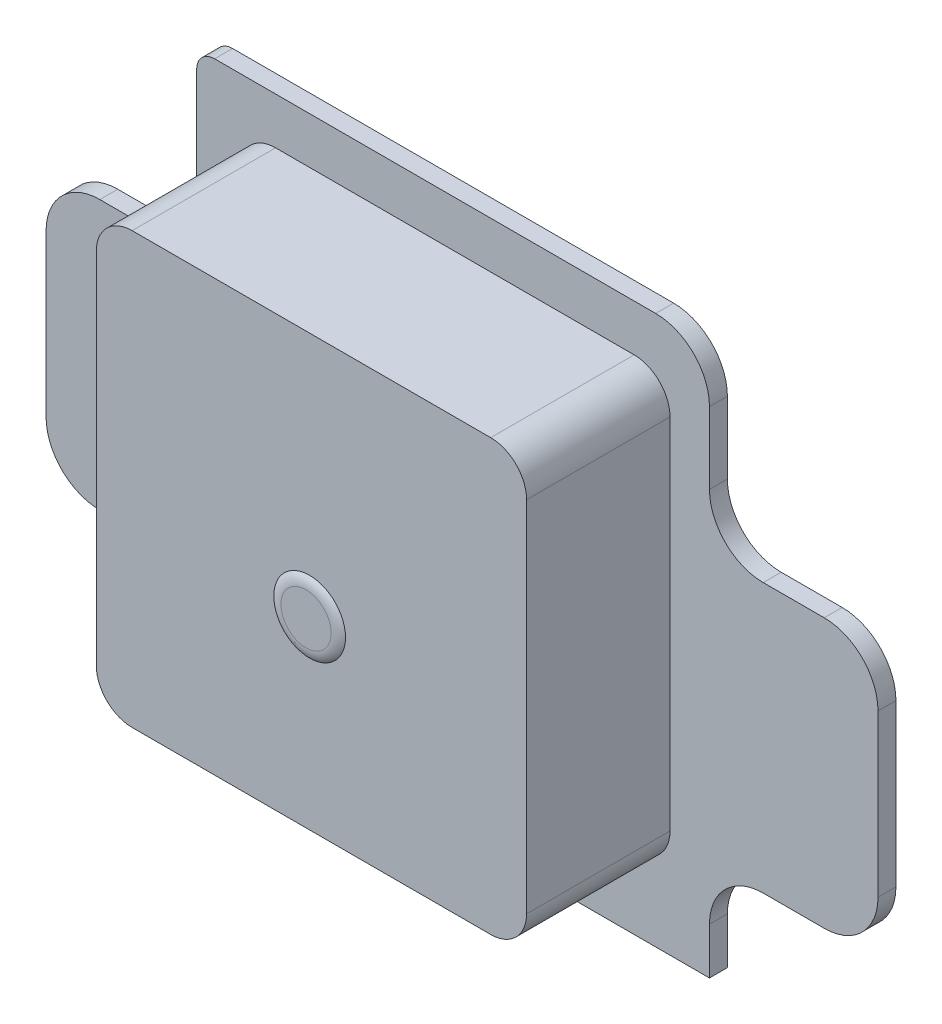
SolidWorks part; units mm, degrees
ref_plane "正面" through (0, 0, 0) normal (0, 0, 1) x (1, 0, 0)
ref_plane "平面" through (0, 0, 0) normal (0, 1, 0) x (1, 0, 0)
ref_plane "右側面" through (0, 0, 0) normal (1, 0, 0) x (0, 0, -1)
sketch "ｽｹｯﾁ1" plane through (0, 0, 0) normal (0, 0, 1) x (1, 0, 0)
  line L1 (-7.15, -7.65) -> (7.15, -7.65)
  line L2 (-7.15, -7.65) -> (-7.15, 7.65)
  line L3 (-7.15, 7.65) -> (7.15, 7.65)
  line L4 (7.15, -7.65) -> (7.15, 7.65)
  line L5 (-7.15, -7.65) -> (7.15, 7.65) construction
  line L6 (-7.15, 7.65) -> (7.15, -7.65) construction
  point P0 (0, 0)
  dimension "D1" = 14.3
  dimension "D2" = 15.3
extrude "ﾎﾞｽ - 押し出し1" add sketch "ｽｹｯﾁ1" along normal blind 0.5
sketch "ｽｹｯﾁ2" plane through (0, 0, 0.5) normal (0, 0, 1) x (1, 0, 0)
  line L0 (-7.15, 7.65) -> (-7.15, -7.65) construction
  line L1 (-7.15, 2.65) -> (-11.35, 2.65)
  line L2 (-7.15, 2.65) -> (-7.15, -4.85)
  line L3 (-7.15, -4.85) -> (-11.35, -4.85)
  line L4 (-11.35, 2.65) -> (-11.35, -4.85)
  line L5 (7.15, -7.65) -> (7.15, 7.65) construction
  line L6 (7.15, 2.65) -> (11.85, 2.65)
  line L7 (7.15, 2.65) -> (7.15, -4.85)
  line L8 (7.15, -4.85) -> (11.85, -4.85)
  line L9 (11.85, 2.65) -> (11.85, -4.85)
  line L10 (7.15, 7.65) -> (-7.15, 7.65) construction
  dimension "D1" = 4.2
  dimension "D2" = 4.7
  dimension "D3" = 7.5
  dimension "D4" = 7.5
  dimension "D5" = 5
  dimension "D6" = 5
extrude "ﾎﾞｽ - 押し出し2" add sketch "ｽｹｯﾁ2" against normal blind 0.5
fillet "ﾌｨﾚｯﾄ1" radius 1.5 9 edges at (7.15, 2.65, 0.25) (11.85, 2.65, 0.25) (11.85, -4.85, 0.25) (7.15, -4.85, 0.25) (-7.15, -4.85, 0.25) (-11.35, -4.85, 0.25) (-11.35, 2.65, 0.25) (-7.15, 2.65, 0.25) (7.15, 7.65, 0.25)
fillet "ﾌｨﾚｯﾄ2" radius 0.5 1 edges at (-7.15, 7.65, 0.25)
sketch "ｽｹｯﾁ3" plane through (0, 0, 0.5) normal (0, 0, 1) x (1, 0, 0)
  line L0 (-7.15, 7.15) -> (-7.15, 4.15) construction
  line L1 (-5.95, 6.35) -> (6.05, 6.35)
  line L2 (-5.95, 6.35) -> (-5.95, -5.65)
  line L3 (-5.95, -5.65) -> (6.05, -5.65)
  line L4 (6.05, 6.35) -> (6.05, -5.65)
  line L6 (-7.15, -7.65) -> (7.15, -7.65) construction
  point P4 (0.05, 6.35)
  point P7 (-5.95, 0.35)
  dimension "D1" = 12
  dimension "D2" = 12
  dimension "D3" = 7.2
  dimension "D4" = 8
extrude "ﾎﾞｽ - 押し出し3" add sketch "ｽｹｯﾁ3" along normal blind 4
fillet "ﾌｨﾚｯﾄ3" radius 1 4 edges at (-5.95, 6.35, 2.5) (6.05, 6.35, 2.5) (6.05, -5.65, 2.5) (-5.95, -5.65, 2.5)
sketch "ｽｹｯﾁ4" plane through (0, 0, 4.5) normal (0, 0, 1) x (1, 0, 0)
  circle A0 centre (0, -0.5) radius 1
  dimension "D1" = 0.5
  dimension "D2" = 2
extrude "ﾎﾞｽ - 押し出し4" add sketch "ｽｹｯﾁ4" along normal blind 0.1
fillet "ﾌｨﾚｯﾄ4" radius 0.5 1 edges at (1, -0.5, 4.6)
